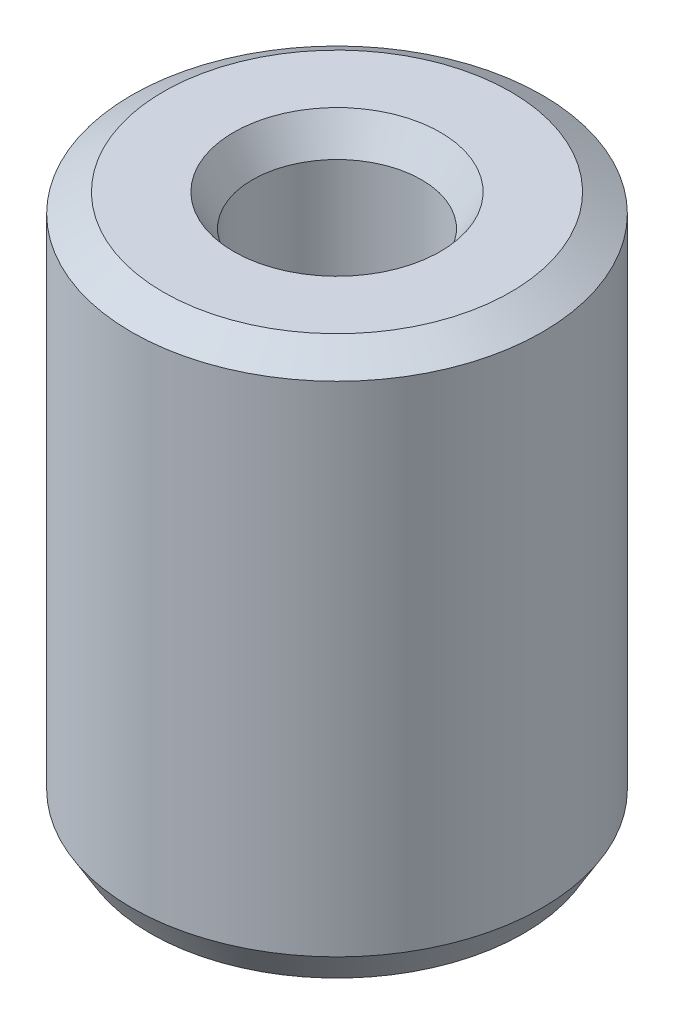
SolidWorks part; units mm, degrees
ref_plane "Front Plane" through (0, 0, 0) normal (0, 0, 1) x (1, 0, 0)
ref_plane "Top Plane" through (0, 0, 0) normal (0, 1, 0) x (1, 0, 0)
ref_plane "Right Plane" through (0, 0, 0) normal (1, 0, 0) x (0, 0, -1)
sketch "Sketch1" plane through (0, 0, 0) normal (0, 1, 0) x (1, 0, 0)
  circle A0 centre (0, 0) radius 7.5
  dimension "SLEEVE_OD" = 15
extrude "Boss-Extrude1" add sketch "Sketch1" along normal blind 20.0534
sketch "Sketch2" plane through (0, 0, 0) normal (0, 1, 0) x (1, 0, 0)
  circle A0 centre (0, 0) radius 3.0873
  dimension "BORE_D" = 6.1746
extrude "Cut-Extrude1" cut sketch "Sketch2" along normal through all
chamfer "Chamfer1" distance 0.6876 angle 59.276 4 edges at (0, 20.0534, 3.0873) (0, 0, 3.0873) (0, 0, 7.5) (0, 20.0534, 7.5) first distance on face at (0, 20.0534, 3.0873) first distance on face at (0, 0, 3.0873) first distance on face at (0, 20.0534, 7.5)
